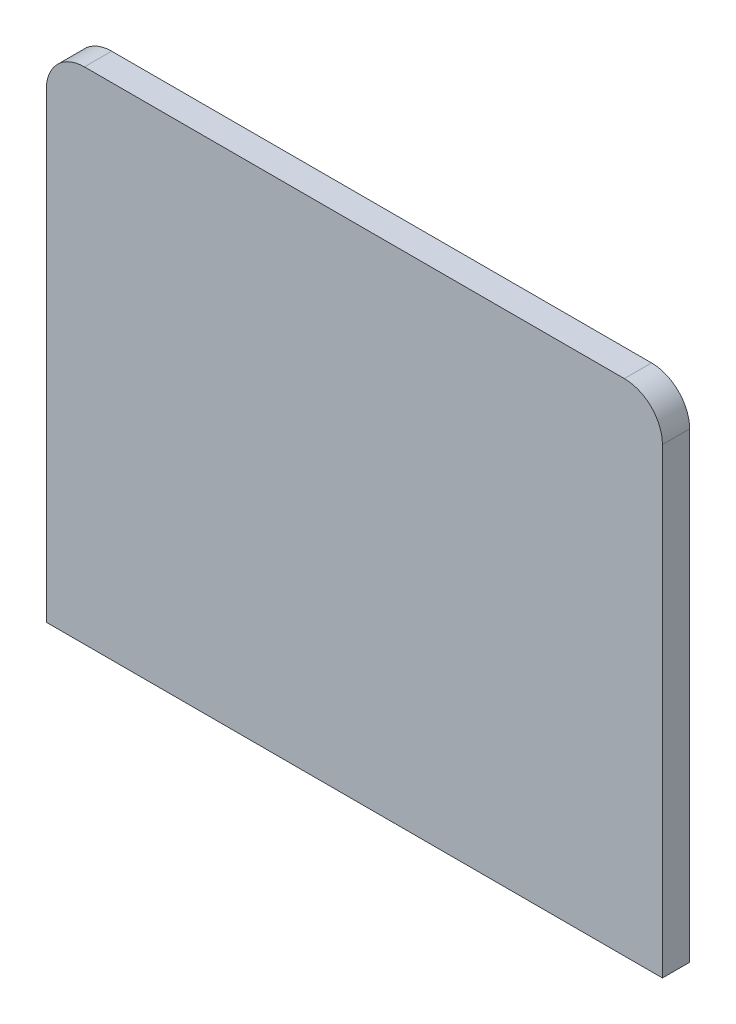
SolidWorks part; units mm, degrees
material "AISI 1020"
ref_plane "Plano frontal" through (0, 0, 0) normal (0, 0, 1) x (1, 0, 0)
ref_plane "Plano superior" through (0, 0, 0) normal (0, 1, 0) x (1, 0, 0)
ref_plane "Plano direito" through (0, 0, 0) normal (1, 0, 0) x (0, 0, -1)
sketch "Esboço1" plane through (0, 0, 0) normal (0, 0, 1) x (1, 0, 0)
  line L1 (-107.95, 0) -> (107.95, 0)
  line L2 (-107.95, 0) -> (-107.95, 161.89)
  line L3 (-94.6, 175.24) -> (94.6, 175.24)
  line L4 (107.95, 0) -> (107.95, 161.89)
  arc A0 (94.6, 175.24) -> (107.95, 161.89) centre (94.6, 161.89) cw
  arc A1 (-107.95, 161.89) -> (-94.6, 175.24) centre (-94.6, 161.89) cw
  point P8 (107.95, 175.24)
  dimension "D3" = 13.35
  dimension "D1" = 215.9
  dimension "D2" = 175.24
base flange "Flange-base1" sketch "Esboço1" thickness 9.53 reverse thickness direction no parameters "D1"=7
sketch "Curva-Linhas1" [suppressed] plane through (0, 0, 0) normal (0, 1, 0) x (1, 0, 0)
sketch "Caixa delimitadora1" [suppressed] plane through (0, 0, 0) normal (0, 1, 0) x (1, 0, 0)
sheet metal parameters "Chapa metálica1" thickness 9.53 parameters "D1"=7
flat pattern "Padrão-Plano1" [suppressed]
sketch "Curva-Linhas2" plane through (0, 0, 0) normal (0, 1, 0) x (1, 0, 0)
sketch3d "Caixa delimitadora2" [suppressed]
  line L0 (13.35, 13.35, 0) -> (-202.55, 13.35, 0) construction
  line L1 (13.35, -161.89, 0) -> (-202.55, -161.89, 0) construction
  line L2 (13.35, 13.35, 0) -> (13.35, -161.89, 0) construction
  line L3 (-202.55, 13.35, 0) -> (-202.55, -161.89, 0) construction
